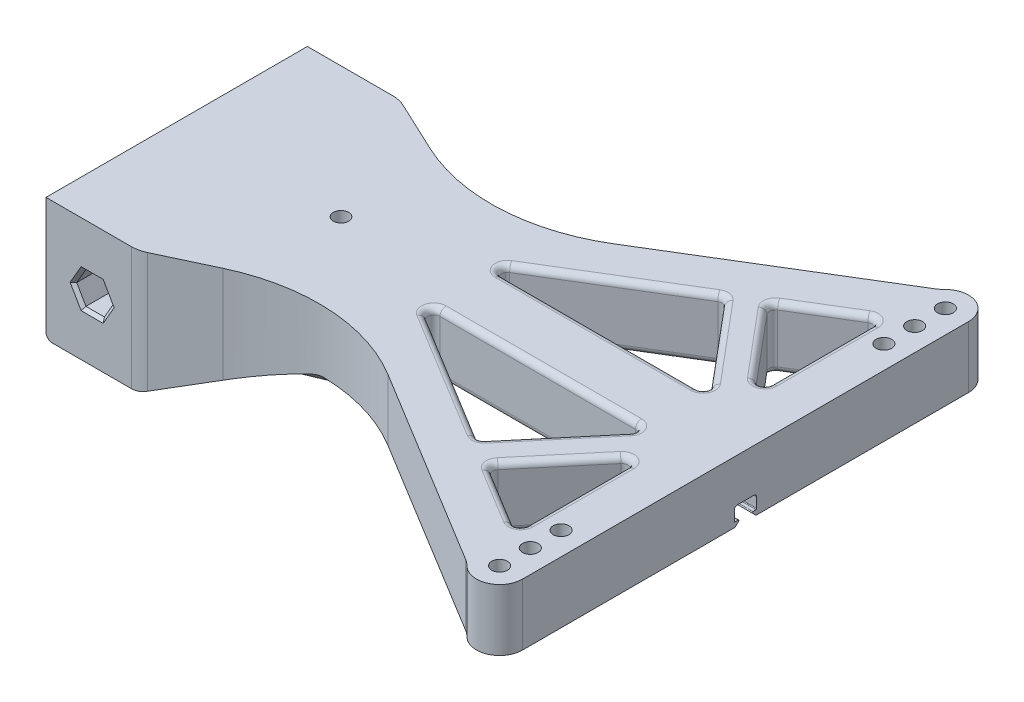
SolidWorks part; units mm, degrees
material "ABS"
ref_plane "Front Plane" through (0, 0, 0) normal (0, 0, 1) x (1, 0, 0)
ref_plane "Top Plane" through (0, 0, 0) normal (0, 1, 0) x (1, 0, 0)
ref_plane "Right Plane" through (0, 0, 0) normal (1, 0, 0) x (0, 0, -1)
sketch "Sketch2" plane through (0, 0, 0) normal (0, 1, 0) x (1, 0, 0)
  circle A0 centre (0, 0) radius 9.525
  circle A1 centre (0, -184.15) radius 9.525
  dimension "D2" = 19.05
  dimension "D1" = 184.15
  dimension "D4" = 0
extrude "Boss-Extrude1" add sketch "Sketch2" along normal blind 25.4
sketch "Sketch3" plane through (0, 25.4, 0) normal (0, 1, 0) x (1, 0, 0)
  line L0 (-9.525, -184.15) -> (-9.525, 0)
  line L1 (9.525, 0) -> (9.525, -184.15)
  circle A1 centre (0, 0) radius 9.525
  arc A2 (9.525, 0) -> (-9.525, 0) centre (0, 0) ccw
  circle A3 centre (0, -184.15) radius 9.525
  arc A4 (-9.525, -184.15) -> (9.525, -184.15) centre (0, -184.15) ccw
  dimension "D1" = 0
  dimension "D2" = 0
extrude "Boss-Extrude2" add sketch "Sketch3" along normal blind 12.7
sketch "Sketch4" plane through (-9.525, 0, 0) normal (-1, 0, 0) x (0, 0, 1)
  line L11 (92.075, 38.1) -> (92.075, 25.4) construction
  line L12 (0, 38.1) -> (184.15, 38.1) construction
  line L13 (0, 25.4) -> (184.15, 25.4) construction
  line L14 (92.075, 38.1) -> (79.375, 38.1)
  line L15 (79.375, 38.1) -> (79.375, 25.4)
  line L16 (79.375, 25.4) -> (92.075, 25.4)
  line L17 (92.075, 25.4) -> (104.775, 25.4)
  line L18 (104.775, 25.4) -> (104.775, 38.1)
  line L19 (104.775, 38.1) -> (92.075, 38.1)
  dimension "D1" = 12.7
  dimension "D2" = 12.7
extrude "Boss-Extrude3" add sketch "Sketch4" along normal blind 177.8
sketch "Sketch5" plane through (-187.325, 0, 0) normal (-1, 0, 0) x (0, 0, 1)
  line L0 (92.075, 38.1) -> (92.075, 25.4) construction
  line L1 (104.775, 38.1) -> (79.375, 38.1) construction
  line L2 (79.375, 25.4) -> (104.775, 25.4) construction
  line L3 (87.3643, 25.4) -> (96.7857, 25.4)
  line L4 (96.1139, 25.6782) -> (94.9126, 26.8795)
  line L5 (95.1248, 27.3917) -> (96.4, 27.3917)
  line L6 (96.7, 27.6917) -> (96.7, 31.6917)
  line L7 (95.4, 32.9917) -> (88.75, 32.9917)
  line L8 (87.45, 31.6917) -> (87.45, 27.6917)
  line L9 (87.75, 27.3917) -> (89.0252, 27.3917)
  line L10 (89.2374, 26.8795) -> (88.0361, 25.6782)
  arc A0 (96.1139, 25.6782) -> (96.7857, 25.4) centre (96.7857, 26.35) ccw
  arc A1 (95.1248, 27.3917) -> (94.9126, 26.8795) centre (95.1248, 27.0917) ccw
  arc A2 (96.4, 27.3917) -> (96.7, 27.6917) centre (96.4, 27.6917) ccw
  arc A3 (96.7, 31.6917) -> (95.4, 32.9917) centre (95.4, 31.6917) ccw
  arc A4 (88.75, 32.9917) -> (87.45, 31.6917) centre (88.75, 31.6917) ccw
  arc A5 (87.45, 27.6917) -> (87.75, 27.3917) centre (87.75, 27.6917) ccw
  arc A6 (89.2374, 26.8795) -> (89.0252, 27.3917) centre (89.0252, 27.0917) ccw
  arc A7 (87.3643, 25.4) -> (88.0361, 25.6782) centre (87.3643, 26.35) ccw
  point P8 (92.075, 25.4)
extrude "Cut-Extrude1" cut sketch "Sketch5" against normal through all
sketch "Sketch6" plane through (0, 25.4, 0) normal (0, -1, 0) x (1, 0, 0)
  line L1 (-225.425, 92.075) -> (-187.325, 92.075) construction
  line L2 (-7.5791, -5.7691) -> (1.8247, 9.3486) construction
  line L20 (-187.325, 92.075) -> (23.5031, 92.075) construction
  line L36 (9.525, 184.15) -> (9.525, 96.7857) construction
  line L39 (-187.325, 104.775) -> (-187.325, 79.375) construction
  line L40 (-187.325, 104.775) -> (-187.325, 79.375) construction
  line L41 (-7.5791, 189.9191) -> (1.8247, 174.8014) construction
  line L42 (-225.425, 38.1) -> (-187.325, 38.1)
  line L43 (-225.425, 38.1) -> (-225.425, 146.05)
  line L44 (-225.425, 146.05) -> (-187.325, 146.05)
  line L45 (-187.325, 79.375) -> (-187.325, 104.775)
  line L46 (-7.5791, -5.7691) -> (-91.4484, 45.3624)
  line L47 (1.8247, 9.3486) -> (-113.0371, 79.375)
  line L48 (-187.325, 38.1) -> (-163.4739, 49.2878)
  line L49 (-187.325, 79.375) -> (-9.525, 79.375) construction
  line L50 (-187.325, 79.375) -> (-113.0371, 79.375)
  line L51 (-187.325, 79.375) -> (-9.525, 79.375) construction
  line L53 (1.8247, 174.8014) -> (-113.0371, 104.775)
  line L54 (-7.5791, 189.9191) -> (-91.4484, 138.7876)
  line L55 (-187.325, 146.05) -> (-163.4739, 134.8622)
  line L56 (-187.325, 104.775) -> (-113.0371, 104.775)
  circle A0 centre (0, 0) radius 9.525 construction
  circle A2 centre (0, 0) radius 9.525
  arc A3 (1.8247, 9.3486) -> (-7.5791, -5.7691) centre (0, 0) ccw
  arc A4 (-9.525, 184.15) -> (9.525, 184.15) centre (0, 184.15) ccw construction
  arc A5 (-9.525, 184.15) -> (1.8247, 174.8014) centre (0, 184.15) ccw
  arc A6 (-9.525, 184.15) -> (-7.5791, 189.9191) centre (0, 184.15) cw
  arc A7 (1.8247, 174.8014) -> (-7.5791, 189.9191) centre (0, 184.15) cw
  arc A8 (-91.4484, 45.3624) -> (-163.4739, 49.2878) centre (-131.114, -19.6997) ccw
  arc A9 (-91.4484, 138.7876) -> (-163.4739, 134.8622) centre (-131.114, 203.8497) cw
  point P29 (-126.4066, 66.675)
  line M8 (-187.325, 104.775) -> (-187.325, 96.7857)
  line M12 (-9.525, 184.15) -> (-9.525, 104.775)
  line M13 (-9.525, 104.775) -> (-187.325, 104.775)
  dimension "D5" = 76.2
  dimension "D1" = 38.1
  dimension "D2" = 107.95
  dimension "D4" = 12.7
  dimension "D6" = 7.7003
  dimension "D7" = 17.1041
  dimension "D8" = 100.9734
  dimension "D3" = 0
extrude "Boss-Extrude4" add sketch "Sketch6" against normal blind 12.7 contours L54 A9 L55 L44 L43 L42 L48 A8 L46 A3 L47 L50 L45 L53 A6 M8 M13 M12
sketch "Sketch10" plane through (0, 0, 0) normal (0, -1, 0) x (1, 0, 0)
  circle A1 centre (0, 0) radius 9.525
  circle A2 centre (0, 0) radius 9.525
  circle A3 centre (0, 184.15) radius 9.525
  circle A4 centre (0, 184.15) radius 9.525
  dimension "D1" = 0
  dimension "D2" = 0
extrude "Cut-Extrude3" cut sketch "Sketch10" against normal blind 25.4
sketch "Sketch11" plane through (0, 25.4, 0) normal (0, -1, 0) x (1, 0, 0)
  line L0 (-6.985, 81.915) -> (-6.985, 14.9549) construction
  line L1 (0, 0) -> (0, 12.7) construction
  line L2 (0, 184.15) -> (0, 171.45) construction
  line L3 (0, 180.9115) -> (0, 3.2385) construction
  circle A0 centre (0, 0) radius 3.2385
  circle A1 centre (0, 12.7) radius 3.2385
  circle A2 centre (0, 25.4) radius 3.2385
  circle A3 centre (0, 184.15) radius 3.2385
  circle A4 centre (0, 171.45) radius 3.2385
  circle A5 centre (0, 158.75) radius 3.2385
  dimension "D1" = 6.477
  dimension "D2" = 6.477
  dimension "D3" = 177.673
  dimension "D5" = 12.7
  dimension "D7" = 12.7
  dimension "D4" = 3
  dimension "D6" = 3
extrude "Cut-Extrude4" cut sketch "Sketch11" against normal through all both and the other way through all
sketch "Sketch19" plane through (0, 25.4, 0) normal (0, 1, 0) x (1, 0, 0)
  line L8 (-225.425, -146.05) -> (-187.325, -146.05) construction
  line L9 (-225.425, -38.1) -> (-225.425, -146.05) construction
  line L10 (-225.425, -38.1) -> (-187.325, -38.1) construction
  line L11 (-225.425, -146.05) -> (-187.325, -146.05)
  line L12 (-225.425, -38.1) -> (-225.425, -146.05)
  line L13 (-225.425, -38.1) -> (-187.325, -38.1)
  line L14 (-187.325, -38.1) -> (-163.4739, -49.2878)
  line L16 (-163.4739, -134.8622) -> (-187.325, -146.05)
  line L17 (-131.114, -56.5003) -> (-131.114, -127.6497)
  arc A0 (-163.4739, -49.2878) -> (-91.4484, -45.3624) centre (-131.114, 19.6997) ccw construction
  arc A1 (-91.4484, -138.7876) -> (-163.4739, -134.8622) centre (-131.114, -203.8497) ccw construction
  arc A2 (-131.114, -127.6497) -> (-163.4739, -134.8622) centre (-131.114, -203.8497) ccw
  arc A3 (-163.4739, -49.2878) -> (-131.114, -56.5003) centre (-131.114, 19.6997) ccw
extrude "Boss-Extrude9" add sketch "Sketch19" against normal blind 25.4
sketch "Sketch22" plane through (0, 0, 0) normal (0, 0, 1) x (1, 0, 0)
  line L7 (-187.325, 0) -> (-131.114, 25.4)
  line L8 (-214.0006, 25.4) -> (-210.1878, 18.796)
  line L15 (-210.1878, 18.796) -> (-202.5622, 18.796)
  line L16 (-202.5622, 18.796) -> (-198.7494, 25.4)
  line L17 (-198.7494, 25.4) -> (-202.5622, 32.004)
  line L18 (-202.5622, 32.004) -> (-210.1878, 32.004)
  line L19 (-210.1878, 32.004) -> (-214.0006, 25.4)
  line L34 (-131.114, 0) -> (-131.114, 25.4) construction
  line L39 (-225.425, 38.1) -> (-187.325, 38.1) construction
  line L40 (-225.425, 38.1) -> (-225.425, 0) construction
  line L41 (-163.4739, 0) -> (-131.114, 0) construction
  line L42 (-163.4739, 0) -> (-187.325, 0) construction
  line L43 (-131.114, 0) -> (-131.114, 25.4)
  line L44 (-163.4739, 0) -> (-131.114, 0)
  line L45 (-163.4739, 0) -> (-187.325, 0)
  circle A0 centre (-206.375, 25.4) radius 6.604 construction
  dimension "D1" = 13.208
  dimension "D2" = 12.7
  dimension "D3" = 19.05
extrude "Cut-Extrude8" cut sketch "Sketch22" against normal through all both and the other way through all
sketch "Sketch25" plane through (0, 38.1, 0) normal (0, 1, 0) x (1, 0, 0)
  line L5 (-9.525, -79.375) -> (-44.557, -37.6255) construction
  line L8 (-39.073, -34.2822) -> (-50.0409, -40.9689)
  line L9 (9.525, -92.075) -> (-92.3846, -92.075) construction
  line L10 (9.525, -184.15) -> (9.525, 0) construction
  line L20 (-113.0371, -79.375) -> (-9.525, -79.375) construction
  line L21 (-9.525, -16.268) -> (-9.525, -79.375) construction
  line L22 (-17.8143, -79.375) -> (-9.525, -79.375)
  line L23 (-9.525, -69.4962) -> (-9.525, -79.375)
  line L24 (-39.073, -34.2822) -> (-9.525, -69.4962)
  line L25 (-9.525, -16.268) -> (-113.0371, -79.375) construction
  line L26 (-17.8143, -79.375) -> (-50.0409, -40.9689)
  line L27 (-9.525, -104.775) -> (-44.557, -146.5245) construction
  line L28 (-17.8143, -104.775) -> (-50.0409, -143.1811)
  line L29 (-39.073, -149.8678) -> (-9.525, -114.6538)
  line L30 (-9.525, -114.6538) -> (-9.525, -104.775)
  line L31 (-17.8143, -104.775) -> (-9.525, -104.775)
  line L32 (-39.073, -149.8678) -> (-50.0409, -143.1811)
  dimension "D1" = 12.7
  dimension "D4" = 40
extrude "Boss-Extrude11" add sketch "Sketch25" against normal blind 12.7
sketch "Sketch29" plane through (0, 38.1, 0) normal (0, 1, 0) x (1, 0, 0)
  line L3 (-17.8143, -104.775) -> (-113.0371, -104.775)
  line L4 (-50.0409, -143.1811) -> (-17.8143, -104.775)
  line L5 (-113.0371, -104.775) -> (-50.0409, -143.1811)
  line L6 (-17.8143, -104.775) -> (-113.0371, -104.775)
  line L7 (-50.0409, -143.1811) -> (-17.8143, -104.775)
  line L8 (-113.0371, -104.775) -> (-50.0409, -143.1811)
  line L9 (-9.525, -16.268) -> (-39.073, -34.2822)
  line L10 (-9.525, -69.4962) -> (-9.525, -16.268)
  line L11 (-39.073, -34.2822) -> (-9.525, -69.4962)
  line L12 (-9.525, -16.268) -> (-39.073, -34.2822)
  line L13 (-9.525, -69.4962) -> (-9.525, -16.268)
  line L14 (-39.073, -34.2822) -> (-9.525, -69.4962)
  line L15 (-17.8143, -79.375) -> (-50.0409, -40.9689)
  line L16 (-113.0371, -79.375) -> (-17.8143, -79.375)
  line L17 (-50.0409, -40.9689) -> (-113.0371, -79.375)
  line L18 (-17.8143, -79.375) -> (-50.0409, -40.9689)
  line L19 (-113.0371, -79.375) -> (-17.8143, -79.375)
  line L20 (-50.0409, -40.9689) -> (-113.0371, -79.375)
  line L21 (-9.525, -114.6538) -> (-39.073, -149.8678)
  line L22 (-9.525, -167.882) -> (-9.525, -114.6538)
  line L23 (-39.073, -149.8678) -> (-9.525, -167.882)
  line L24 (-9.525, -114.6538) -> (-39.073, -149.8678)
  line L25 (-9.525, -167.882) -> (-9.525, -114.6538)
  line L26 (-39.073, -149.8678) -> (-9.525, -167.882)
  line L32 (-91.4484, -138.7876) -> (-7.5791, -189.9191)
  line L33 (9.525, -184.15) -> (9.525, 0)
  line L34 (-7.5791, 5.7691) -> (-91.4484, -45.3624)
  line L35 (-163.4739, -49.2878) -> (-187.325, -38.1)
  line L36 (-187.325, -38.1) -> (-225.425, -38.1)
  line L37 (-225.425, -38.1) -> (-225.425, -146.05)
  line L39 (-187.325, -146.05) -> (-163.4739, -134.8622)
  line L40 (-91.4484, -138.7876) -> (-7.5791, -189.9191)
  line L41 (9.525, -184.15) -> (9.525, 0)
  line L42 (-7.5791, 5.7691) -> (-91.4484, -45.3624)
  line L43 (-163.4739, -49.2878) -> (-187.325, -38.1)
  line L44 (-187.325, -38.1) -> (-225.425, -38.1)
  line L47 (-187.325, -146.05) -> (-163.4739, -134.8622)
  line L48 (-225.425, -38.1) -> (-225.425, -146.05)
  line L50 (-225.425, -146.05) -> (-187.325, -146.05)
  line L51 (-225.425, -146.05) -> (-187.325, -146.05)
  circle A1 centre (0, -171.45) radius 3.2385
  circle A2 centre (0, -171.45) radius 3.2385
  circle A3 centre (0, -25.4) radius 3.2385
  circle A4 centre (0, -25.4) radius 3.2385
  circle A5 centre (0, -12.7) radius 3.2385
  circle A6 centre (0, -12.7) radius 3.2385
  circle A7 centre (0, -184.15) radius 3.2385
  circle A8 centre (0, -184.15) radius 3.2385
  circle A9 centre (0, -158.75) radius 3.2385
  circle A10 centre (0, -158.75) radius 3.2385
  circle A11 centre (0, 0) radius 3.2385
  circle A12 centre (0, 0) radius 3.2385
  arc A16 (-7.5791, -189.9191) -> (9.525, -184.15) centre (0, -184.15) ccw
  arc A17 (9.525, 0) -> (-7.5791, 5.7691) centre (0, 0) ccw
  arc A18 (-163.4739, -49.2878) -> (-91.4484, -45.3624) centre (-131.114, 19.6997) ccw
  arc A19 (-91.4484, -138.7876) -> (-163.4739, -134.8622) centre (-131.114, -203.8497) ccw
  arc A20 (-7.5791, -189.9191) -> (9.525, -184.15) centre (0, -184.15) ccw
  arc A21 (9.525, 0) -> (-7.5791, 5.7691) centre (0, 0) ccw
  arc A22 (-163.4739, -49.2878) -> (-91.4484, -45.3624) centre (-131.114, 19.6997) ccw
  arc A23 (-91.4484, -138.7876) -> (-163.4739, -134.8622) centre (-131.114, -203.8497) ccw
  dimension "D1" = 0
  dimension "D2" = 0
  dimension "D3" = 0
  dimension "D4" = 0
  dimension "D5" = 0
  dimension "D6" = 0
  dimension "D7" = 0
  dimension "D8" = 0
  dimension "D9" = 0
  dimension "D10" = 0
  dimension "D11" = 0
extrude "Boss-Extrude13" add sketch "Sketch29" along normal blind 12.7
fillet "Fillet6" radius 2.54 36 edges at (-24.299, 25.4, 25.2751) (-24.299, 25.4, 158.8749) (-9.525, 38.1, 167.882) (-113.0371, 38.1, 104.775) (-9.525, 38.1, 16.268) (-81.539, 25.4, 60.1719) (-17.8143, 38.1, 79.375) (-50.0409, 38.1, 40.9689) (-39.073, 38.1, 34.2822) (-9.525, 38.1, 69.4962) (-33.9276, 25.4, 60.1719) (-24.299, 25.4, 51.8892) (-81.539, 25.4, 123.9781) (-9.525, 25.4, 141.2679) (-39.073, 38.1, 149.8678) (-33.9276, 25.4, 123.9781) (-50.0409, 38.1, 143.1811) (-17.8143, 38.1, 104.775) (-24.299, 25.4, 132.2608) (-9.525, 38.1, 114.6538) (-81.539, 50.8, 123.9781) (-33.9276, 50.8, 123.9781) (-65.4257, 50.8, 104.775) (-24.299, 50.8, 51.8892) (-9.525, 50.8, 42.8821) (-24.299, 50.8, 25.2751) (-81.539, 50.8, 60.1719) (-65.4257, 50.8, 79.375) (-33.9276, 50.8, 60.1719) (-24.299, 50.8, 158.8749) (-9.525, 50.8, 141.2679) (-24.299, 50.8, 132.2608) (-65.4257, 25.4, 104.775) (-65.4257, 25.4, 79.375) (-9.525, 25.4, 42.8821) (-113.0371, 38.1, 79.375)
sketch "Sketch23" plane through (-187.325, 0, 0) normal (1, 0, 0) x (0, 0, -1)
  line L8 (-88.0361, 25.6782) -> (-89.2374, 26.8795)
  line L9 (-89.0252, 27.3917) -> (-87.75, 27.3917)
  line L10 (-87.45, 27.6917) -> (-87.45, 31.6917)
  line L11 (-88.75, 32.9917) -> (-95.4, 32.9917)
  line L12 (-96.7, 31.6917) -> (-96.7, 27.6917)
  line L13 (-96.4, 27.3917) -> (-95.1248, 27.3917)
  line L14 (-94.9126, 26.8795) -> (-96.1139, 25.6782)
  line L15 (-96.7857, 25.4) -> (-87.3643, 25.4)
  line L16 (-88.0361, 25.6782) -> (-89.2374, 26.8795)
  line L17 (-89.0252, 27.3917) -> (-87.75, 27.3917)
  line L18 (-87.45, 27.6917) -> (-87.45, 31.6917)
  line L19 (-88.75, 32.9917) -> (-95.4, 32.9917)
  line L20 (-96.7, 31.6917) -> (-96.7, 27.6917)
  line L21 (-96.4, 27.3917) -> (-95.1248, 27.3917)
  line L22 (-94.9126, 26.8795) -> (-96.1139, 25.6782)
  line L24 (-96.7857, 25.4) -> (-87.3643, 25.4)
  arc A8 (-88.0361, 25.6782) -> (-87.3643, 25.4) centre (-87.3643, 26.35) ccw
  arc A9 (-89.0252, 27.3917) -> (-89.2374, 26.8795) centre (-89.0252, 27.0917) ccw
  arc A10 (-87.75, 27.3917) -> (-87.45, 27.6917) centre (-87.75, 27.6917) ccw
  arc A11 (-87.45, 31.6917) -> (-88.75, 32.9917) centre (-88.75, 31.6917) ccw
  arc A12 (-95.4, 32.9917) -> (-96.7, 31.6917) centre (-95.4, 31.6917) ccw
  arc A13 (-96.7, 27.6917) -> (-96.4, 27.3917) centre (-96.4, 27.6917) ccw
  arc A14 (-94.9126, 26.8795) -> (-95.1248, 27.3917) centre (-95.1248, 27.0917) ccw
  arc A15 (-96.7857, 25.4) -> (-96.1139, 25.6782) centre (-96.7857, 26.35) ccw
  arc A16 (-88.0361, 25.6782) -> (-87.3643, 25.4) centre (-87.3643, 26.35) ccw
  arc A17 (-89.0252, 27.3917) -> (-89.2374, 26.8795) centre (-89.0252, 27.0917) ccw
  arc A18 (-87.75, 27.3917) -> (-87.45, 27.6917) centre (-87.75, 27.6917) ccw
  arc A19 (-87.45, 31.6917) -> (-88.75, 32.9917) centre (-88.75, 31.6917) ccw
  arc A20 (-95.4, 32.9917) -> (-96.7, 31.6917) centre (-95.4, 31.6917) ccw
  arc A21 (-96.7, 27.6917) -> (-96.4, 27.3917) centre (-96.4, 27.6917) ccw
  arc A22 (-94.9126, 26.8795) -> (-95.1248, 27.3917) centre (-95.1248, 27.0917) ccw
  arc A23 (-96.7857, 25.4) -> (-96.1139, 25.6782) centre (-96.7857, 26.35) ccw
  dimension "D1" = 0
extrude "Boss-Extrude10" add sketch "Sketch23" along normal blind 76.2
fillet "Fillet14" radius 12.7 4 edges at (-187.325, 0, 92.075) (-131.114, 25.4, 92.075) (-187.325, 25.4, 38.1) (-187.325, 25.4, 146.05)
fillet "Fillet15" radius 2.54 1 edges at (-225.425, 0, 92.075)
sketch "Sketch31" plane through (0, 50.8, 0) normal (0, 1, 0) x (1, 0, 0)
  line L0 (-225.425, -92.075) -> (9.525, -92.075) construction
  line L1 (-225.425, -38.1) -> (-225.425, -146.05) construction
  line L2 (9.525, -184.15) -> (9.525, 0) construction
  line L8 (-175.8442, -79.375) -> (-150.4442, -79.375)
  line L9 (-175.8442, -79.375) -> (-175.8442, -104.775)
  line L10 (-175.8442, -104.775) -> (-150.4442, -104.775)
  line L11 (-150.4442, -79.375) -> (-150.4442, -104.775)
  point P7 (-163.1442, -79.375)
  dimension "D1" = 12.7
  dimension "D2" = 25.4
  dimension "D3" = 62.2808
  dimension "D4" = 25.4
extrude "Boss-Extrude14" add sketch "Sketch31" against normal blind 48.4251
chamfer "Chamfer1" distance 13.208 angle 45 2 edges at (-163.1442, 10.9265, 79.375) (-163.1442, 10.9265, 104.775)
chamfer "Chamfer2" distance 3.175 angle 45 1 edges at (-150.4442, 16.6653, 92.075)
sketch "Sketch33" plane through (0, 2.3749, 0) normal (0, -1, 0) x (1, 0, 0)
  line L0 (-150.4442, 92.075) -> (-248.8881, 92.075) construction
  line L1 (-150.4442, 104.9604) -> (-150.4442, 79.1896) construction
  circle A0 centre (-157.5562, 92.075) radius 3.175
  dimension "D1" = 6.35
  dimension "D2" = 7.112
extrude "Cut-Extrude9" cut sketch "Sketch33" against normal through all
chamfer "Chamfer3" distance 1.27 angle 45 12 edges at (-200.6558, 28.702, 146.05) (-206.375, 32.004, 146.05) (-212.0942, 28.702, 146.05) (-212.0942, 22.098, 146.05) (-206.375, 18.796, 146.05) (-200.6558, 22.098, 146.05) (-206.375, 32.004, 38.1) (-212.0942, 28.702, 38.1) (-212.0942, 22.098, 38.1) (-206.375, 18.796, 38.1) (-200.6558, 22.098, 38.1) (-200.6558, 28.702, 38.1)
fillet "Fillet18" radius 12.7 2 edges at (-7.5791, 38.1, -5.7691) (-7.5791, 38.1, 189.9191)
fillet "Fillet19" radius 12.7 1 edges at (-175.8442, 5.1878, 92.075)
